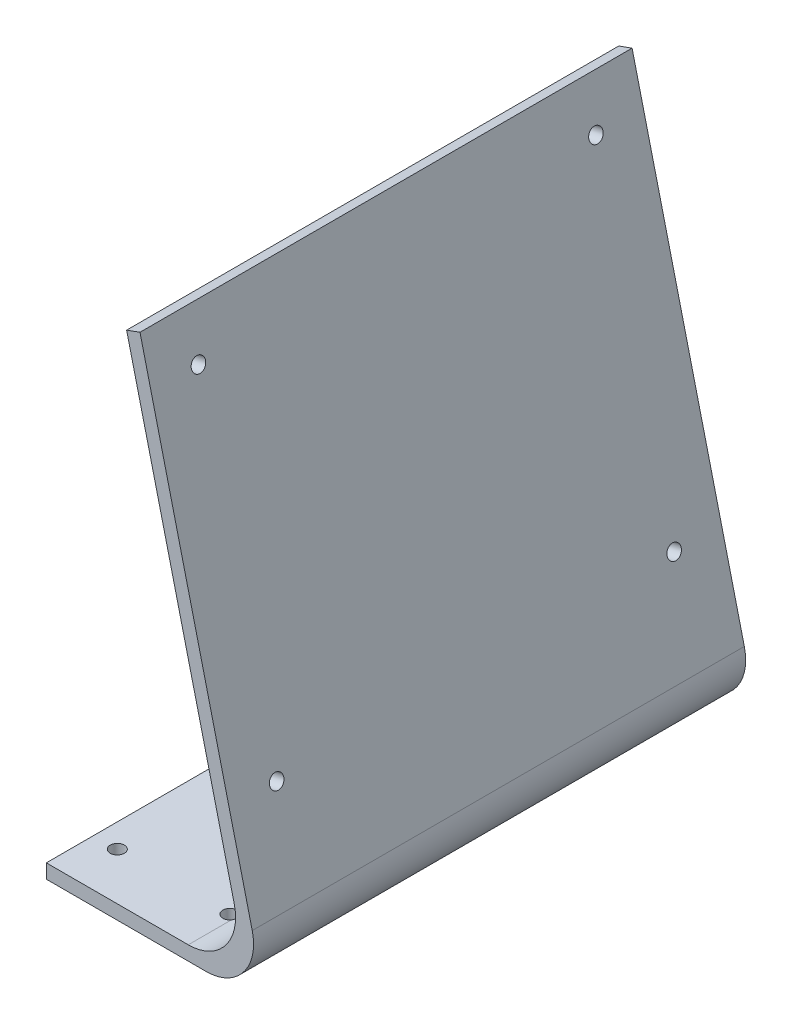
SolidWorks part; units mm, degrees
ref_plane "Front Plane" through (0, 0, 0) normal (0, 0, 1) x (1, 0, 0)
ref_plane "Top Plane" through (0, 0, 0) normal (0, 1, 0) x (1, 0, 0)
ref_plane "Right Plane" through (0, 0, 0) normal (1, 0, 0) x (0, 0, -1)
sketch "Sketch1" plane through (0, 0, 0) normal (0, 0, 1) x (1, 0, 0)
  line L0 (-50.53, 0) -> (-50.53, 3)
  line L1 (-50.53, 3) -> (-20.53, 3)
  line L2 (-50.53, 0) -> (-16.7319, 0)
  line L3 (-7.0146, 12.361) -> (-30.7379, 110)
  line L4 (-30.7379, 110) -> (-33.5595, 108.9811)
  line L5 (-33.5595, 108.9811) -> (-10.8127, 15.361)
  arc A0 (-10.8127, 15.361) -> (-20.53, 3) centre (-20.53, 13) cw
  arc A1 (-16.7319, 0) -> (-7.0146, 12.361) centre (-16.7319, 10) ccw
  dimension "D1" = 10
  dimension "D2" = 3
  dimension "D3" = 30
  dimension "D4" = 110
extrude "Boss-Extrude1" add sketch "Sketch1" along normal mid plane 104
sketch "Эскиз1" plane through (-3.7876, -0.9203, 0) normal (0.9717, 0.2361, 0) x (0, 0, -1)
  line L0 (-52, 114.1474) -> (52, 114.1474) construction
  line L1 (-47, 109.1474) -> (47, 109.1474) construction
  line L2 (-47, 109.1474) -> (-47, 29.1474) construction
  line L3 (-47, 29.1474) -> (47, 29.1474) construction
  line L4 (47, 109.1474) -> (47, 29.1474) construction
  line L5 (-47, 109.1474) -> (47, 29.1474) construction
  line L6 (-47, 29.1474) -> (47, 109.1474) construction
  line L7 (-52, 13.6677) -> (-52, 114.1474) construction
  point P0 (0, 69.1474)
  dimension "D1" = 80
  dimension "D2" = 94
  dimension "D3" = 5
  dimension "D4" = 5
sketch "Эскиз2" plane through (-3.7876, -0.9203, 0) normal (0.9717, 0.2361, 0) x (0, 0, -1)
  line L0 (-47, 109.1474) -> (-47, 29.1474) construction
  line L1 (-47, 109.1474) -> (47, 109.1474) construction
  line L2 (0, 69.1474) -> (0, 79.7671) construction
  line L3 (-47, 109.1474) -> (47, 29.1474) construction
  line L4 (0, 69.1474) -> (-10.9608, 69.1474) construction
  circle A0 centre (-42, 104.1474) radius 1.5
  circle A1 centre (42, 104.1474) radius 1.5
  circle A2 centre (42, 34.1474) radius 1.5
  circle A3 centre (-42, 34.1474) radius 1.5
  dimension "D1" = 5
  dimension "D2" = 5
extrude "Вырез-Вытянуть1" cut sketch "Эскиз2" against normal up to next
sketch "Sketch2" plane through (0, 0, 0) normal (0, -1, 0) x (1, 0, 0)
  line L0 (0, 0) -> (-74.033, 0) construction
  line L1 (-33.63, 33.8413) -> (-33.63, -3.8536) construction
  line L3 (-50.53, 52) -> (-50.53, -52) construction
  circle A0 centre (-45.53, 42) radius 1.5
  circle A1 centre (-21.73, 42) radius 1.5
  circle A2 centre (-21.73, -42) radius 1.5
  circle A3 centre (-45.53, -42) radius 1.5
  dimension "D2" = 5
  dimension "D3" = 42
  dimension "D1" = 16.9
extrude "Cut-Extrude1" cut sketch "Sketch2" against normal up to next
